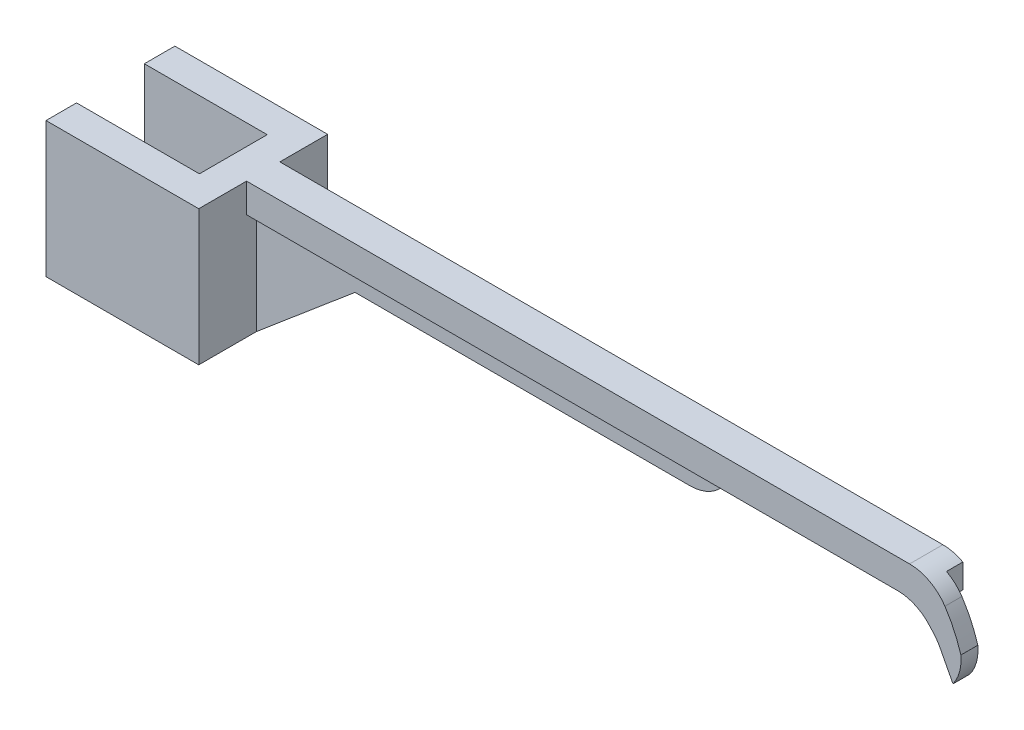
SolidWorks part; units mm, degrees
ref_plane "Front Plane" through (0, 0, 0) normal (0, 0, 1) x (1, 0, 0)
ref_plane "Top Plane" through (0, 0, 0) normal (0, 1, 0) x (1, 0, 0)
ref_plane "Right Plane" through (0, 0, 0) normal (1, 0, 0) x (0, 0, -1)
sketch "Sketch1" plane through (0, 0, 0) normal (0, 1, 0) x (1, 0, 0)
  line L1 (-30, 3.75) -> (30, 3.75)
  line L2 (-30, 3.75) -> (-30, -3.75)
  line L3 (-30, -3.75) -> (30, -3.75)
  line L4 (30, 3.75) -> (30, -3.75)
  line L5 (-30, 3.75) -> (30, -3.75) construction
  line L6 (-30, -3.75) -> (30, 3.75) construction
  point P1 (0, 0)
  dimension "D1" = 60
  dimension "D2" = 7.5
extrude "Boss-Extrude1" add sketch "Sketch1" along normal blind 13
sketch "Sketch3" plane through (0, 13, 0) normal (0, 1, 0) x (1, 0, 0)
  line L0 (-30, 2.5) -> (-18, 2.5)
  line L1 (-30, 3.75) -> (-30, -3.75) construction
  line L2 (0, 0) -> (-30, 0) construction
  line L3 (-18, 2.5) -> (-18, -2.5)
  line L4 (-30, -2.5) -> (-18, -2.5)
  line L5 (-30, 2.5) -> (-30, -2.5)
  dimension "D1" = 2.5
  dimension "D2" = 12
extrude "Cut-Extrude1" cut sketch "Sketch3" against normal blind 10.5
sketch "Sketch4" plane through (0, 2.5, 0) normal (0, 1, 0) x (1, 0, 0)
  line L0 (-21, 0) -> (-26.7, 0)
  line L2 (-18, 0) -> (-21, 0)
  line L3 (-18, -2.5) -> (-18, 2.5) construction
  circle A0 centre (-21, 0) radius 1
  circle A1 centre (-26.7, 0) radius 1
  dimension "D2" = 2
  dimension "D4" = 2
  dimension "D1" = 3
  dimension "D3" = 5.7
extrude "Cut-Extrude2" cut sketch "Sketch4" against normal blind 10 contours A1 | L2 A0 L0 | L0 A0 L2 | A0 region at (-21, 2.5, 0.4244) region at (-21, 2.5, -0.4244) region at (-27.6717, 2.5, 0)
sketch "Sketch9" plane through (0, 0, 0) normal (0, -1, 0) x (1, 0, 0)
  line L0 (30, 0) -> (-18, 0) construction
  line L1 (30, 3.75) -> (30, -3.75) construction
  line L2 (30, 1.6) -> (-15.2776, 1.6)
  line L6 (-15.2776, 1.6) -> (-15.2776, 3.75)
  line L7 (-30, 3.75) -> (30, 3.75) construction
  line L8 (-15.2776, 3.75) -> (30, 3.75)
  line L9 (30, 3.75) -> (30, 1.6)
  line L10 (30, -3.75) -> (30, -1.6)
  line L11 (-15.2776, -3.75) -> (30, -3.75)
  line L12 (-15.2776, -1.6) -> (-15.2776, -3.75)
  line L13 (30, -1.6) -> (-15.2776, -1.6)
  dimension "D1" = 48
  dimension "D2" = 1.6
extrude "Cut-Extrude8" cut sketch "Sketch9" against normal blind 15
sketch "Sketch13" plane through (0, 0, 0) normal (0, -1, 0) x (1, 0, 0)
  line L0 (30, 1.6) -> (-15.2776, 1.6)
  line L1 (-15.2776, 1.6) -> (-15.2776, -1.6)
  line L2 (-15.2776, -1.6) -> (30, -1.6)
  line L3 (30, -1.6) -> (30, 1.6)
extrude "Cut-Extrude10" cut sketch "Sketch13" against normal blind 8
sketch "Sketch14" plane through (0, 8, 0) normal (0, -1, 0) x (1, 0, 0)
  line L0 (30, 0) -> (-15.2776, 0) construction
  line L1 (30, -1.6) -> (30, 1.6) construction
  line L2 (-15.2776, 1.6) -> (-15.2776, -1.6) construction
  line L3 (30, 0.65) -> (-15.2776, 0.65)
  line L4 (-15.2776, 3.75) -> (-15.2776, -3.75) construction
  line L5 (-15.2776, 0.65) -> (-15.2776, 1.6)
  line L6 (-15.2776, 1.6) -> (30, 1.6)
  line L7 (30, 1.6) -> (30, 0.65)
  line L8 (30, -1.6) -> (30, -0.65)
  line L9 (-15.2776, -1.6) -> (30, -1.6)
  line L10 (-15.2776, -0.65) -> (-15.2776, -1.6)
  line L11 (30, -0.65) -> (-15.2776, -0.65)
  dimension "D1" = 0.65
extrude "Cut-Extrude11" cut sketch "Sketch14" against normal blind 2.2
sketch "Sketch16" plane through (0, 0, 0) normal (0, 0, 1) x (1, 0, 0)
  line L0 (-5.8022, 8) -> (-15.2776, 0)
  line L1 (-15.2776, 8) -> (30, 8) construction
rib "Rib10" sketch "Sketch16" sketch "Sketch16" thickness 1.3 extrusion direction parallel to sketch draft on no parameters "D1"=1.3
sketch "Sketch17" plane through (0, 0, -1.6) normal (0, 0, -1) x (-1, 0, 0)
  line L0 (-30, 11.6) -> (-25.9962, 8)
  line L1 (-30, 13) -> (-30, 10.2) construction
  line L2 (-30, 8) -> (5.8022, 8) construction
  line L3 (-25.9962, 8) -> (-30, 8)
  line L4 (-30, 8) -> (-30, 11.6)
sketch "Sketch20" plane through (0, 2.5, 0) normal (0, 1, 0) x (1, 0, 0)
  line L0 (-30, 2.5) -> (-18, 2.5)
  line L1 (-18, 2.5) -> (-18, -2.5)
  line L2 (-18, -2.5) -> (-18, 2.5) construction
  line L3 (-18, -2.5) -> (-30, -2.5)
  line L4 (-30, -2.5) -> (-30, 2.5)
extrude "Boss-Extrude3" add sketch "Sketch20" along normal blind 3
sketch "Sketch22" plane through (0, 5.5, 0) normal (0, 1, 0) x (1, 0, 0)
  line L0 (-30, 2.5) -> (-18, 2.5)
  line L1 (-18, 2.5) -> (-18, -2.5)
  line L2 (-18, -2.5) -> (-30, -2.5)
  line L3 (-30, -2.5) -> (-30, 2.5)
extrude "Cut-Extrude13" cut sketch "Sketch22" against normal blind 1.95
sketch "Sketch23" plane through (0, 0, 0) normal (0, -1, 0) x (1, 0, 0)
  circle A0 centre (-26.7, 0) radius 1
  circle A1 centre (-21, 0) radius 1
extrude "Cut-Extrude14" cut sketch "Sketch23" against normal blind 10
scale "Scale1" scale about centroid uniform scaling yes scale factor 1.6
scale "Scale3" scale about centroid uniform scaling yes scale factor 0.8
scale "Scale4" scale about centroid uniform scaling yes scale factor 0.958904
sketch "Sketch34" plane through (0, 2.6491, 0) normal (0, 1, 0) x (1, 0, 0)
  line L3 (-19.8893, -4) -> (-19.8893, 4)
  line L4 (-19.8893, 4) -> (-34.4354, 4)
  line L5 (-34.4354, 4.6027) -> (-34.4354, 3.0685) construction
  line L6 (-34.4354, 4) -> (-34.4354, -4)
  line L9 (-19.8893, -4) -> (-34.4354, -4)
extrude "Cut-Extrude20" cut sketch "Sketch34" along normal blind 15
sketch "Sketch36" plane through (0, 10.8113, 0) normal (0, -1, 0) x (1, 0, 0)
  line L0 (-16.3651, 1.9638) -> (-16.3651, 0.7978)
sketch "Sketch39" plane through (39.2085, 0, 0) normal (1, 0, 0) x (0, 0, -1)
  line L0 (-1.9638, 14.248) -> (1.9638, 14.248)
  line L1 (1.9638, 14.248) -> (1.9638, 10.8113)
  line L2 (1.9638, 14.248) -> (1.9638, 10.8113) construction
  line L3 (1.9638, 14.248) -> (1.9638, 10.8113) construction
  line L4 (1.9638, 10.8113) -> (-1.9638, 10.8113)
  line L5 (-1.9638, 10.8113) -> (-1.9638, 14.248)
extrude "Boss-Extrude5" add sketch "Sketch39" along normal blind 25
sketch "Sketch45" plane through (0, 0, 1.9638) normal (0, 0, 1) x (1, 0, 0)
  line L0 (64.2085, 14.248) -> (67.1979, 11.2586)
  line L1 (67.1979, 11.2586) -> (67.9032, 7.967)
  line L2 (67.9032, 7.967) -> (68.2444, 4.4087)
  line L3 (68.2444, 4.4087) -> (65.7032, 8.6494)
  line L4 (65.7032, 8.6494) -> (64.2085, 10.8113)
  line L5 (64.2085, 10.8113) -> (64.2085, 14.248)
extrude "Boss-Extrude6" add sketch "Sketch45" against normal blind 2
fillet "Fillet1" radius 15 1 edges at (67.1979, 11.2586, 0.9638)
fillet "Fillet3" radius 5 1 edges at (64.2078, 14.248, 0)
sketch "Sketch47" plane through (0, 0, 1.9638) normal (0, 0, 1) x (1, 0, 0)
  line L0 (62.6817, 10.8113) -> (65.1375, 8.079)
  line L1 (64.2085, 10.8113) -> (-16.3651, 10.8113) construction
  line L2 (65.1375, 8.079) -> (66.9741, 4.5502)
  line L3 (66.9741, 4.5502) -> (68.2444, 4.4087)
  line L4 (68.2444, 4.4087) -> (67.9032, 7.967) construction
  line L5 (68.2444, 4.4087) -> (65.7032, 8.6494)
  line L6 (65.7032, 8.6494) -> (64.2085, 10.8113)
  line L7 (64.2085, 10.8113) -> (62.6817, 10.8113)
extrude "Boss-Extrude7" add sketch "Sketch47" against normal blind 2
fillet "Fillet4" radius 5 1 edges at (62.6817, 10.8113, 0.9638)
fillet "Fillet5" radius 5 1 edges at (65.1375, 8.079, 0.9638)
fillet "Fillet6" radius 5 1 edges at (68.2444, 4.4087, 0.9638)
fillet "Fillet7" radius 5 1 edges at (39.2085, 8.1111, 0)
sketch "Sketch49" plane through (0, 2.6491, 0) normal (0, 1, 0) x (1, 0, 0)
  line L0 (-19.7066, 0) -> (-23.3888, 0)
  line L1 (-19.7066, -3.0685) -> (-19.7066, 3.0685) construction
  line L2 (-23.3888, 0) -> (-30.385, 0)
sketch "Sketch52" plane through (-34.4354, 0, 0) normal (-1, 0, 0) x (0, 0, 1)
  line L0 (-4.6027, 14.248) -> (4.6027, 14.248)
  line L1 (4.6027, 14.248) -> (4.6027, -1.7081)
  line L2 (4.6027, -1.7081) -> (-4.6027, -1.7081)
  line L3 (-4.6027, -1.7081) -> (-4.6027, 14.248)
extrude "Cut-Extrude21" cut sketch "Sketch52" against normal blind 0.05
sketch "Sketch54" plane through (0, 2.6491, 0) normal (0, 1, 0) x (1, 0, 0)
  line L0 (-19.8893, 3.0685) -> (-19.8893, -3.0685)
  line L1 (-19.8893, -3.0685) -> (-19.7066, -3.0685)
  line L2 (-19.7066, -3.0685) -> (-19.7066, 3.0685)
  line L3 (-19.7066, 3.0685) -> (-19.8893, 3.0685)
extrude "Boss-Extrude8" add sketch "Sketch54" along normal blind 15
sketch "Sketch55" plane through (-19.7066, 0, 0) normal (1, 0, 0) x (0, 0, -1)
  line L0 (-3.0685, 14.248) -> (-3.0685, 17.6491)
  line L1 (-3.0685, 17.6491) -> (3.0685, 17.6491)
  line L2 (3.0685, 17.6491) -> (3.0685, 14.248)
  line L3 (3.0685, 14.248) -> (-3.0685, 14.248)
extrude "Cut-Extrude22" cut sketch "Sketch55" against normal blind 15
sketch "Sketch57" plane through (0, 14.248, 0) normal (0, 1, 0) x (1, 0, 0)
  line L0 (-34.3854, 4) -> (-19.8893, 4)
  line L1 (-19.8893, 4) -> (-19.8893, -4)
  line L2 (-19.8893, -4) -> (-34.3854, -4)
  line L3 (-34.3854, -4) -> (-34.3854, 4)
extrude "Cut-Extrude23" cut sketch "Sketch57" against normal blind 12.16
sketch "Sketch58" plane through (0, 0, 4.6027) normal (0, 0, 1) x (1, 0, 0)
  line L0 (-34.3854, 14.248) -> (-16.3651, 14.248)
  line L1 (-16.3651, 14.248) -> (-16.3651, -1.7081)
  line L2 (-16.3651, -1.7081) -> (-34.3854, -1.7081)
  line L3 (-34.3854, -1.7081) -> (-34.3854, 14.248)
extrude "Boss-Extrude9" add sketch "Sketch58" along normal blind 3
sketch "Sketch59" plane through (0, 0, -4.6027) normal (0, 0, -1) x (-1, 0, 0)
  line L0 (16.3651, 14.248) -> (34.3854, 14.248)
  line L1 (34.3854, 14.248) -> (34.3854, -1.7081)
  line L2 (34.3854, -1.7081) -> (16.3651, -1.7081)
  line L3 (16.3651, -1.7081) -> (16.3651, 14.248)
extrude "Boss-Extrude10" add sketch "Sketch59" along normal blind 3
